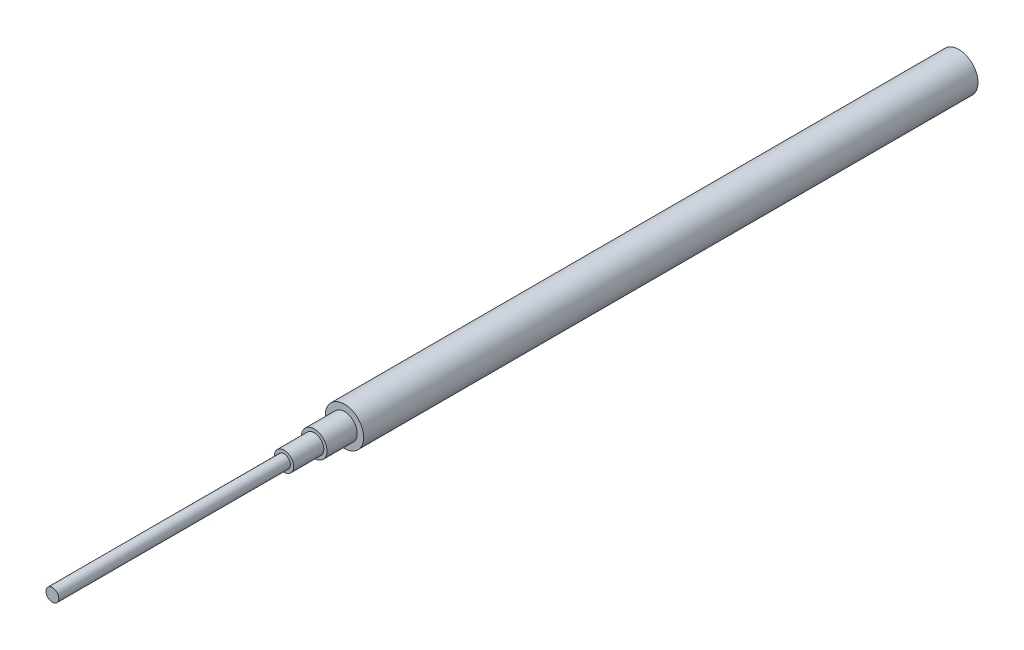
SolidWorks part; units mm, degrees
material "Plain Carbon Steel"
ref_plane "Front Plane" through (0, 0, 0) normal (0, 0, 1) x (1, 0, 0)
ref_plane "Top Plane" through (0, 0, 0) normal (0, 1, 0) x (1, 0, 0)
ref_plane "Right Plane" through (0, 0, 0) normal (1, 0, 0) x (0, 0, -1)
sketch "Sketch1" plane through (0, 0, 0) normal (0, 0, 1) x (1, 0, 0)
  circle A0 centre (0, 0) radius 4.7625
  dimension "D1" = 9.525
extrude "Boss-Extrude1" add sketch "Sketch1" along normal blind 152.5
sketch "Sketch2" plane through (0, 0, 0) normal (0, 0, 1) x (1, 0, 0)
  circle A0 centre (0, 0) radius 3.175
  dimension "D1" = 6.35
extrude "Boss-Extrude2" add sketch "Sketch2" along normal blind 160
sketch "Sketch3" plane through (0, 0, 0) normal (0, 0, 1) x (1, 0, 0)
  circle A0 centre (0, 0) radius 2.3812
  dimension "D1" = 4.7625
extrude "Boss-Extrude3" add sketch "Sketch3" along normal blind 167.5
sketch "Sketch4" plane through (0, 0, 0) normal (0, 0, 1) x (1, 0, 0)
  circle A0 centre (0, 0) radius 1.5875
  dimension "D1" = 3.175
extrude "Boss-Extrude4" add sketch "Sketch4" along normal blind 225
